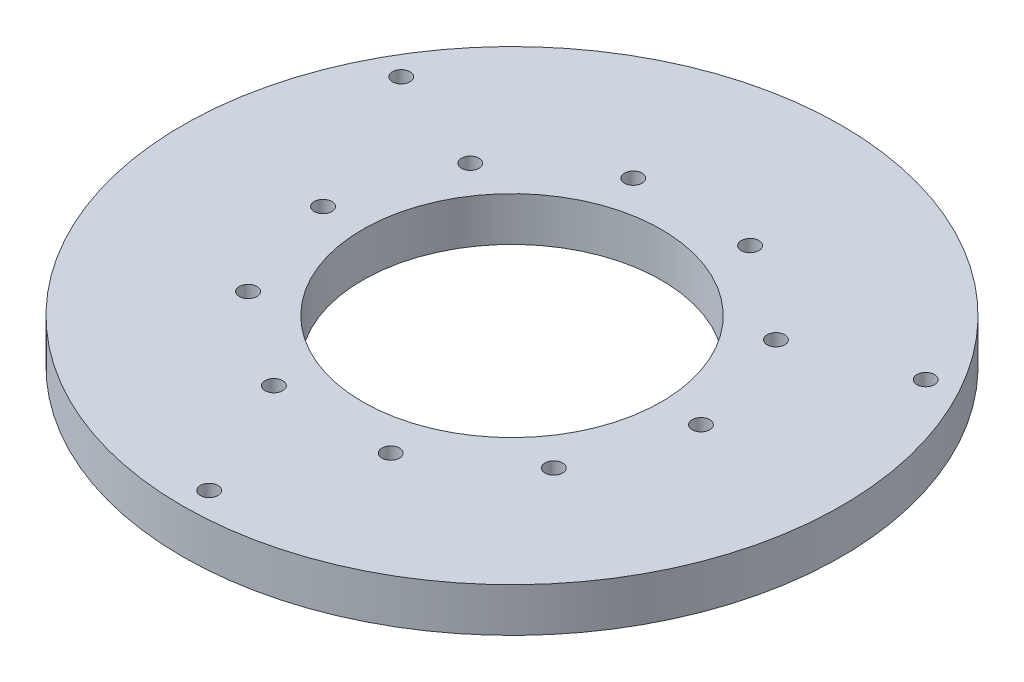
SolidWorks part; units mm, degrees
ref_plane "Front Plane" through (0, 0, 0) normal (0, 0, 1) x (1, 0, 0)
ref_plane "Top Plane" through (0, 0, 0) normal (0, 1, 0) x (1, 0, 0)
ref_plane "Right Plane" through (0, 0, 0) normal (1, 0, 0) x (0, 0, -1)
sketch "Sketch1" plane through (0, 0, 0) normal (0, 1, 0) x (1, 0, 0)
  circle A0 centre (0, 0) radius 37.5
  dimension "D1" = 75
extrude "Boss-Extrude1" add sketch "Sketch1" against normal blind 5
sketch "Sketch2" plane through (0, 0, 0) normal (0, 1, 0) x (1, 0, 0)
  line L0 (-2.75, 0) -> (2.75, 0) construction
  line L1 (0, 39.8902) -> (0, -39.5701) construction
  line L2 (0, -2.75) -> (0, 2.75) construction
  line L4 (-39.7283, 0) -> (39.0263, 0) construction
  circle A0 centre (-21.5, 0) radius 1
  circle A1 centre (-17.3939, 12.6374) radius 1
  circle A2 centre (-6.6439, 20.4477) radius 1
  circle A3 centre (6.6439, 20.4477) radius 1
  circle A4 centre (17.3939, 12.6374) radius 1
  circle A5 centre (21.5, 0) radius 1
  circle A6 centre (17.3939, -12.6374) radius 1
  circle A7 centre (6.6439, -20.4477) radius 1
  circle A8 centre (-6.6439, -20.4477) radius 1
  circle A9 centre (-17.3939, -12.6374) radius 1
  dimension "D1" = 10
  dimension "D2" = 43
extrude "Cut-Extrude1" cut sketch "Sketch2" against normal up to next
sketch "Sketch4" plane through (0, -5, 0) normal (0, -1, 0) x (1, 0, 0)
  line L0 (-15.5255, 11.28) -> (-15.2841, 13.5767)
  line L1 (-19.1906, 0) -> (-20.3453, 2)
  line L2 (-20.3453, 2) -> (-22.6547, 2)
  line L3 (-22.6547, 2) -> (-23.8094, 0)
  line L4 (-23.8094, 0) -> (-22.6547, -2)
  line L5 (-22.6547, -2) -> (-20.3453, -2)
  line L6 (-20.3453, -2) -> (-19.1906, 0)
  line L7 (-15.2841, 13.5767) -> (-17.1525, 14.9341)
  line L8 (-17.1525, 14.9341) -> (-19.2622, 13.9948)
  line L9 (-19.2622, 13.9948) -> (-19.5036, 11.6981)
  line L10 (-19.5036, 11.6981) -> (-17.6353, 10.3406)
  line L11 (-17.6353, 10.3406) -> (-15.5255, 11.28)
  line L12 (-5.9302, 18.2513) -> (-4.3849, 19.9676)
  line L13 (-4.3849, 19.9676) -> (-5.0986, 22.1639)
  line L14 (-5.0986, 22.1639) -> (-7.3575, 22.6441)
  line L15 (-7.3575, 22.6441) -> (-8.9028, 20.9279)
  line L16 (-8.9028, 20.9279) -> (-8.1892, 18.7315)
  line L17 (-8.1892, 18.7315) -> (-5.9302, 18.2513)
  line L18 (5.9302, 18.2513) -> (8.1892, 18.7315)
  line L19 (8.1892, 18.7315) -> (8.9028, 20.9279)
  line L20 (8.9028, 20.9279) -> (7.3575, 22.6441)
  line L21 (7.3575, 22.6441) -> (5.0986, 22.1639)
  line L22 (5.0986, 22.1639) -> (4.3849, 19.9676)
  line L23 (4.3849, 19.9676) -> (5.9302, 18.2513)
  line L24 (15.5255, 11.28) -> (17.6353, 10.3406)
  line L25 (17.6353, 10.3406) -> (19.5036, 11.6981)
  line L26 (19.5036, 11.6981) -> (19.2622, 13.9948)
  line L27 (19.2622, 13.9948) -> (17.1525, 14.9341)
  line L28 (17.1525, 14.9341) -> (15.2841, 13.5767)
  line L29 (15.2841, 13.5767) -> (15.5255, 11.28)
  line L30 (19.1906, 0) -> (20.3453, -2)
  line L31 (20.3453, -2) -> (22.6547, -2)
  line L32 (22.6547, -2) -> (23.8094, 0)
  line L33 (23.8094, 0) -> (22.6547, 2)
  line L34 (22.6547, 2) -> (20.3453, 2)
  line L35 (20.3453, 2) -> (19.1906, 0)
  line L36 (15.5255, -11.28) -> (15.2841, -13.5767)
  line L37 (15.2841, -13.5767) -> (17.1525, -14.9341)
  line L38 (17.1525, -14.9341) -> (19.2622, -13.9948)
  line L39 (19.2622, -13.9948) -> (19.5036, -11.6981)
  line L40 (19.5036, -11.6981) -> (17.6353, -10.3406)
  line L41 (17.6353, -10.3406) -> (15.5255, -11.28)
  line L42 (5.9302, -18.2513) -> (4.3849, -19.9676)
  line L43 (4.3849, -19.9676) -> (5.0986, -22.1639)
  line L44 (5.0986, -22.1639) -> (7.3575, -22.6441)
  line L45 (7.3575, -22.6441) -> (8.9028, -20.9279)
  line L46 (8.9028, -20.9279) -> (8.1892, -18.7315)
  line L47 (8.1892, -18.7315) -> (5.9302, -18.2513)
  line L48 (-5.9302, -18.2513) -> (-8.1892, -18.7315)
  line L49 (-8.1892, -18.7315) -> (-8.9028, -20.9279)
  line L50 (-8.9028, -20.9279) -> (-7.3575, -22.6441)
  line L51 (-7.3575, -22.6441) -> (-5.0986, -22.1639)
  line L52 (-5.0986, -22.1639) -> (-4.3849, -19.9676)
  line L53 (-4.3849, -19.9676) -> (-5.9302, -18.2513)
  line L54 (-15.5255, -11.28) -> (-17.6353, -10.3406)
  line L55 (-17.6353, -10.3406) -> (-19.5036, -11.6981)
  line L56 (-19.5036, -11.6981) -> (-19.2622, -13.9948)
  line L57 (-19.2622, -13.9948) -> (-17.1525, -14.9341)
  line L58 (-17.1525, -14.9341) -> (-15.2841, -13.5767)
  line L59 (-15.2841, -13.5767) -> (-15.5255, -11.28)
  circle A0 centre (-21.5, 0) radius 2 construction
  dimension "D1" = 10
extrude "Cut-Extrude2" cut sketch "Sketch4" against normal blind 1.6
sketch "Sketch6" plane through (0, 0, 0) normal (0, 1, 0) x (1, 0, 0)
  circle A0 centre (0, 0) radius 17
  dimension "D1" = 34
extrude "Cut-Extrude3" cut sketch "Sketch6" against normal up to next
sketch "Sketch7" plane through (0, 0, 0) normal (0, 1, 0) x (1, 0, 0)
  line L0 (0, -32.4389) -> (0, -37.9681) construction
  line L1 (-3, -37.3798) -> (3, -37.3798) construction
  line L2 (-3, -37.3798) -> (-3, -31.5382) construction
  line L3 (-3, -31.5382) -> (3, -31.5382) construction
  line L4 (3, -37.3798) -> (3, -31.5382) construction
  line L5 (0, -2.75) -> (0, 2.75) construction
  line L6 (-3.8774, -34.459) -> (4.357, -34.459) construction
  circle A0 centre (0, 0) radius 37.5 construction
  circle A1 centre (0, -34.459) radius 1
  circle A2 centre (-29.8424, 17.2295) radius 1
  circle A3 centre (29.8424, 17.2295) radius 1
  dimension "D1" = 3
extrude "Cut-Extrude4" cut sketch "Sketch7" against normal up to surface (5 mm away) up to face at (0, -5, 17)
